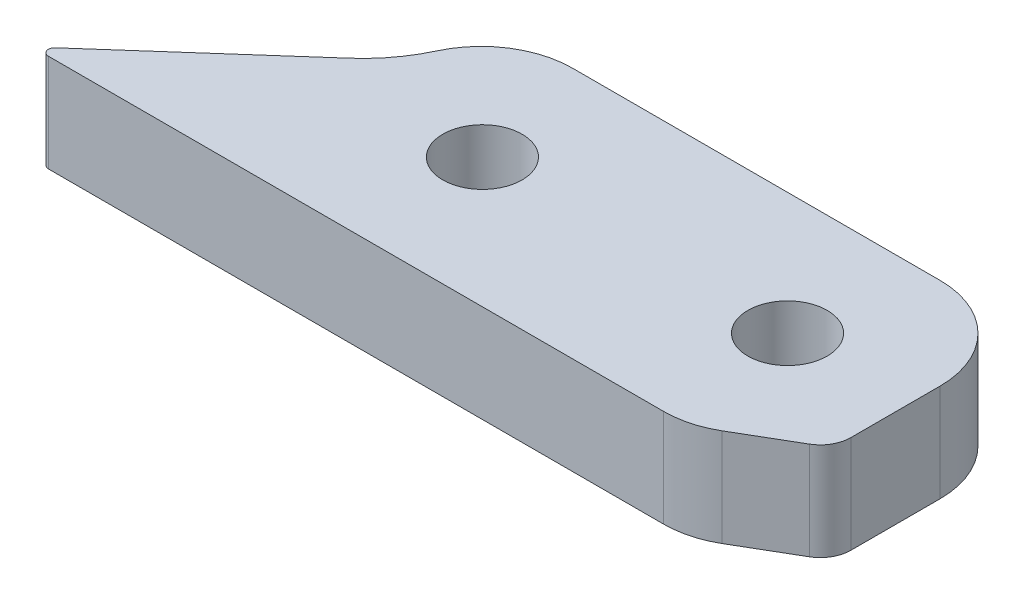
SolidWorks part; units mm, degrees
material "Titanium Ti-8Mn, Annealed"
ref_plane "Front Plane" through (0, 0, 0) normal (0, 0, 1) x (1, 0, 0)
ref_plane "Top Plane" through (0, 0, 0) normal (0, 1, 0) x (1, 0, 0)
ref_plane "Right Plane" through (0, 0, 0) normal (1, 0, 0) x (0, 0, -1)
sketch "Sketch1" plane through (0, 0, 0) normal (0, 1, 0) x (1, 0, 0)
  line L5 (36, -13) -> (36, 0)
  line L6 (36, 0) -> (0, 0)
  line L8 (36, -13) -> (30, -16.5)
  line L9 (30, -16.5) -> (-1.4555, -16.5)
  line L10 (0, 0) -> (0, -5)
  line L11 (0, -5) -> (-13, -16.5)
  line L12 (-13, -16.5) -> (-1.4555, -16.5)
  circle A0 centre (28, -8) radius 2.6
  circle A1 centre (8, -8) radius 2.6
  dimension "D8" = 5.2
  dimension "D9" = 5.2
  dimension "D1" = 13
  dimension "D2" = 36
  dimension "D3" = 8
  dimension "D4" = 13
  dimension "D5" = 5
  dimension "D6" = 8.5
  dimension "D7" = 6
  dimension "D10" = 20
  dimension "D11" = 8
extrude "Boss-Extrude1" add sketch "Sketch1" along normal blind 6.4
fillet "Fillet1" radius 6 3 edges at (30, 3.2, 16.5) (36, 3.2, 0) (0, 3.2, 0)
fillet "Fillet2" radius 10 1 edges at (0, 3.2, 5)
fillet "Fillet3" radius 0.4 1 edges at (-13, 3.2, 16.5)
fillet "Fillet4" radius 2 1 edges at (36, 3.2, 13)
